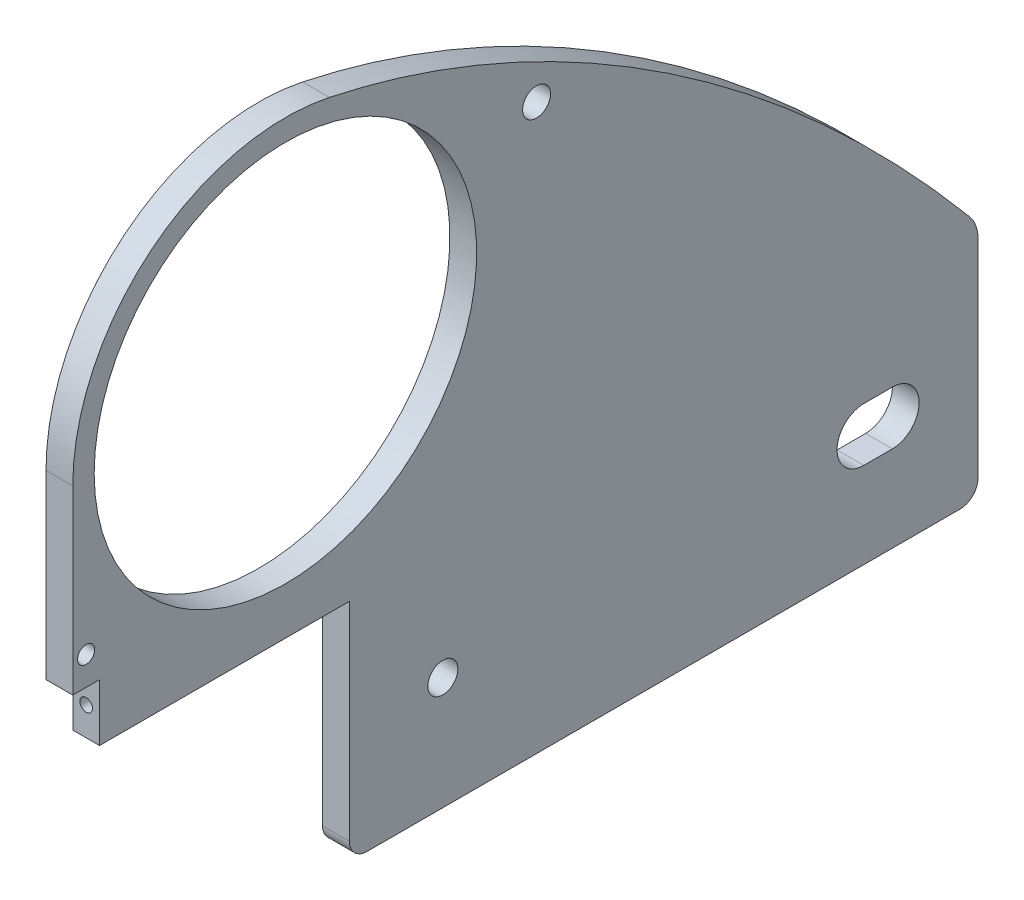
SolidWorks part; units mm, degrees
ref_plane "Front Plane" through (0, 0, 0) normal (0, 0, 1) x (1, 0, 0)
ref_plane "Top Plane" through (0, 0, 0) normal (0, 1, 0) x (1, 0, 0)
ref_plane "Right Plane" through (0, 0, 0) normal (1, 0, 0) x (0, 0, -1)
sketch "Sketch1" plane through (0, 0, 0) normal (1, 0, 0) x (0, 0, -1)
  line L0 (-28.1703, 0) -> (77.3828, 0)
  line L1 (80.5578, 3.175) -> (80.5578, 40.132)
  line L2 (-80.5578, 82.55) -> (-80.5578, 50.292)
  line L4 (-75.7953, 50.292) -> (-75.7953, 40.132)
  line L5 (65.3178, 20.066) -> (60.2378, 20.066) construction
  line L6 (65.3178, 15.3035) -> (60.2378, 15.3035)
  line L7 (-75.7953, 40.132) -> (-31.3453, 40.132)
  line L10 (-31.3453, 40.132) -> (-31.3453, 3.175)
  line L11 (-80.5578, 50.292) -> (-75.7953, 50.292)
  line L12 (65.3178, 24.8285) -> (60.2378, 24.8285)
  arc A0 (65.3178, 15.3035) -> (65.3178, 24.8285) centre (65.3178, 20.066) ccw
  circle A1 centre (-42.7078, 82.55) radius 31.5 construction
  circle A2 centre (65.3178, 20.066) radius 76.2 construction
  circle A3 centre (-78.1765, 55.372) radius 1.524
  arc A4 (60.2378, 24.8285) -> (60.2378, 15.3035) centre (60.2378, 20.066) ccw
  arc A5 (-34.8673, 119.579) -> (-80.5578, 82.55) centre (-42.7078, 82.55) ccw
  arc A6 (-28.1703, 0) -> (-31.3453, 3.175) centre (-28.1703, 3.175) cw
  arc A7 (77.3828, 0) -> (80.5578, 3.175) centre (77.3828, 3.175) ccw
  arc A8 (80.5578, 40.132) -> (79.0734, 44.2123) centre (74.2078, 40.132) ccw
  circle A9 centre (1.9922, 100.457) radius 2.4892
  circle A10 centre (1.9922, 100.457) radius 5.5562 construction
  circle A11 centre (-14.6922, 20.066) radius 2.667
  circle A16 centre (-42.7078, 82.55) radius 34.04
  spline S0 degree 3 poles (-34.8673, 119.579) (-0.0583, 112.2086) (41.2638, 89.2986) (79.0734, 44.2123) knots 0 0 0 0 1 1 1 1
  spline S1 degree 3 poles (79.0888, 44.1938) (50.6675, 78.3472) (10.808, 109.6876) (-34.6964, 119.5424) knots 0 0 0 0 1 1 1 1 construction
  point P13 (62.7778, 20.066)
  point P28 (80.5578, 40.132)
  dimension "D4" = 9.525
  dimension "D7" = 4.7625
  dimension "D8" = 63
  dimension "D9" = 6.35
  dimension "D12" = 3.175
  dimension "D13" = 6.35
  dimension "D14" = 2.54
  dimension "D15" = 152.4
  dimension "D18" = 5.334
  dimension "D19" = 5.08
  dimension "D20" = 82.55
  dimension "D17" = 3.048
  dimension "D24" = 4.9784
  dimension "D25" = 11.1125
  dimension "D2" = 40.132
  dimension "D3" = 20.066
  dimension "D5" = 15.24
  dimension "D6" = 44.45
  dimension "D10" = 161.1156
  dimension "D11" = 95.25
  dimension "D21" = 5.08
  dimension "D22" = 10.16
  dimension "D16" = 2.3813
  dimension "D23" = 60.325
extrude "Boss-Extrude1" add sketch "Sketch1" along normal blind 4.7625
sketch "Sketch2" plane through (0, 0, 75.7953) normal (0, 0, 1) x (1, 0, 0)
  line L0 (0, 50.292) -> (0, 40.132) construction
  line L1 (4.7625, 40.132) -> (0, 40.132) construction
  circle A0 centre (2.3813, 45.212) radius 1.1303
  point P4 (0, 45.212)
  point P7 (2.3813, 40.132)
  dimension "D1" = 2.2606
extrude "Cut-Extrude1" cut sketch "Sketch2" against normal blind 6.35
